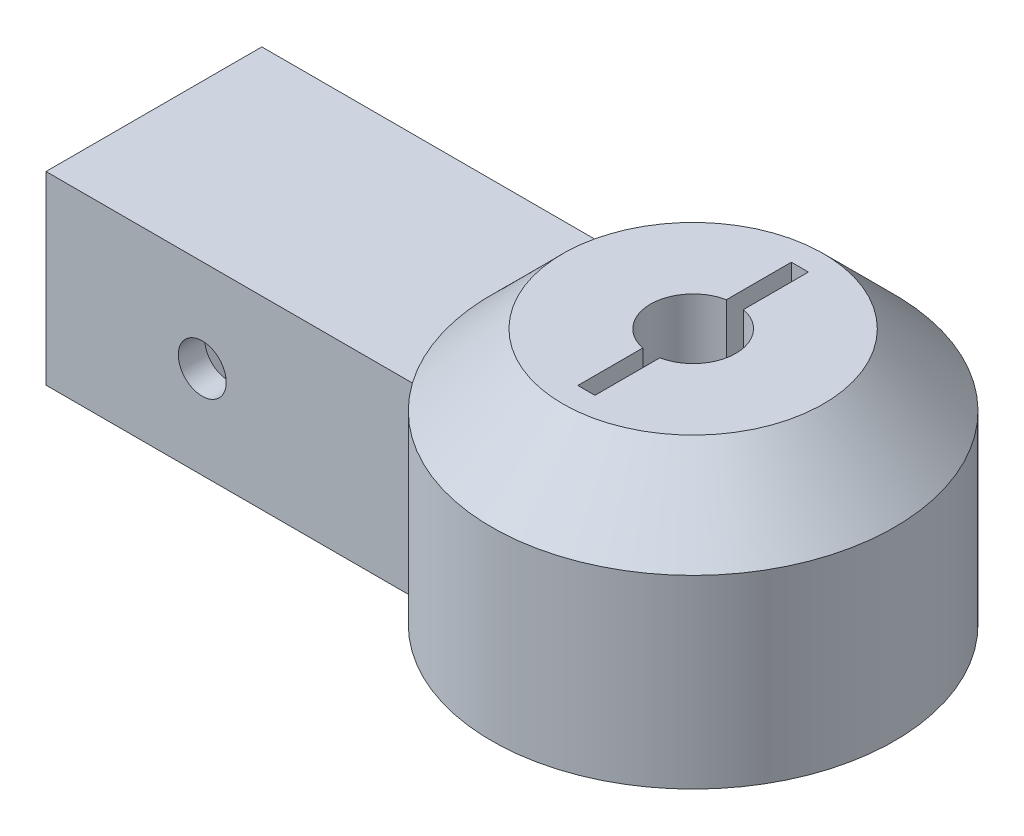
SolidWorks part; units mm, degrees
ref_plane "Plano frontal" through (0, 0, 0) normal (0, 0, 1) x (1, 0, 0)
ref_plane "Plano superior" through (0, 0, 0) normal (0, 1, 0) x (1, 0, 0)
ref_plane "Plano direito" through (0, 0, 0) normal (1, 0, 0) x (0, 0, -1)
sketch "Esboço2" plane through (0, 0, 0) normal (0, 1, 0) x (1, 0, 0)
  line L1 (-55, 0) -> (55, 0) construction
  line L4 (-12.2973, 7) -> (-37.2973, 7)
  line L5 (-37.2973, -8.161) -> (-37.2973, 7)
  line L8 (-37.2973, -8.161) -> (-11.5594, -8.161)
  circle A0 centre (0, 0) radius 11.15
  arc A1 (-11.5594, -8.161) -> (-12.2973, 7) centre (0, 0) ccw
  dimension "D1" = 22.3
  dimension "D3" = 7
  dimension "D2" = 3
  dimension "D4" = 25
extrude "Ressalto-extrusão1" add sketch "Esboço2" along normal blind 13
sketch "Esboço3" plane through (-37.2973, 0, 0) normal (-1, 0, 0) x (0, 0, 1)
  line L0 (0, -55) -> (0, 55) construction
  line L1 (3.5, 3) -> (-3.5, 3)
  line L2 (3.5, 3) -> (3.5, 10)
  line L3 (3.5, 10) -> (-3.5, 10)
  line L4 (-3.5, 3) -> (-3.5, 10)
  line L5 (3.5, 3) -> (-3.5, 10) construction
  line L6 (3.5, 10) -> (-3.5, 3) construction
  point P0 (0, 6.5)
extrude "Corte-extrusão1" cut sketch "Esboço3" against normal blind 26
sketch "Esboço7" plane through (0, 0, 3.5) normal (0, 0, -1) x (-1, 0, 0)
  line L0 (26.3212, 13) -> (26.3212, 0) construction
  line L1 (22.6262, 6.5) -> (24.4737, 3.3)
  line L2 (24.4737, 3.3) -> (28.1688, 3.3)
  line L3 (28.1688, 3.3) -> (30.0163, 6.5)
  line L4 (30.0163, 6.5) -> (28.1688, 9.7)
  line L5 (28.1688, 9.7) -> (24.4737, 9.7)
  line L6 (24.4737, 9.7) -> (22.6262, 6.5)
  line L7 (37.2973, 13) -> (11.5594, 13) construction
  line L8 (37.2973, 0) -> (11.5594, 0) construction
  circle A0 centre (26.3212, 6.5) radius 3.2 construction
extrude "Corte-extrusão2" cut sketch "Esboço7" against normal blind 2.8
sketch "Esboço10" plane through (0, 0, 6.3) normal (0, 0, -1) x (-1, 0, 0)
  line L0 (24.4737, 9.7) -> (28.1688, 3.3) construction
  circle A0 centre (26.3212, 6.5) radius 1.6837
  point P7 (26.3212, 6.5)
extrude "Corte-extrusão3" cut sketch "Esboço10" against normal blind 2.8
sketch "Esboço11" plane through (0, 13, 0) normal (0, 1, 0) x (1, 0, 0)
  line L0 (0, -7.5) -> (0, 7.5) construction
  line L1 (0.6, -7.5) -> (0.6, -2.9394)
  line L2 (-0.6, -7.5) -> (-0.6, -2.9394)
  line L3 (0.6, -7.5) -> (-0.6, -7.5)
  line L4 (0.6, 7.5) -> (-0.6, 7.5)
  line L5 (-0.6, -7.5) -> (-0.6, 7.5) construction
  line L6 (0.6, 2.9394) -> (0.6, 7.5)
  line L7 (0.6, -7.5) -> (0.6, 7.5) construction
  line L8 (-0.6, 2.9394) -> (-0.6, 7.5)
  circle A0 centre (0, 0) radius 14.15
  arc A1 (-0.6, 2.9394) -> (-0.6, -2.9394) centre (0, 0) ccw
  arc A2 (0.6, -2.9394) -> (0.6, 2.9394) centre (0, 0) ccw
  point P7 (0, 0)
  dimension "D1" = 6
  dimension "D2" = 15
  dimension "D3" = 0.6
  dimension "D4" = 0.6
extrude "Ressalto-extrusão2" add sketch "Esboço11" along normal blind 5
chamfer "Chanfro1" distance 5 angle 45 1 edges at (0, 18, 14.15)
